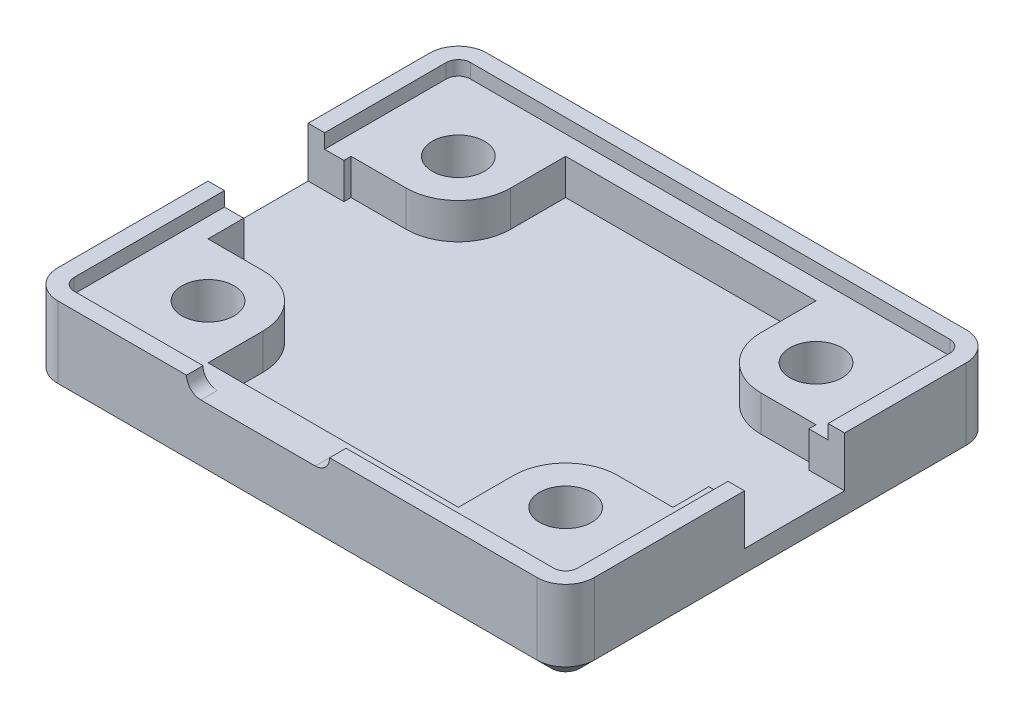
SolidWorks part; units mm, degrees
ref_plane "Front Plane" through (0, 0, 0) normal (0, 0, 1) x (1, 0, 0)
ref_plane "Top Plane" through (0, 0, 0) normal (0, 1, 0) x (1, 0, 0)
ref_plane "Right Plane" through (0, 0, 0) normal (1, 0, 0) x (0, 0, -1)
sketch "Sketch1" plane through (0, 0, 0) normal (0, 1, 0) x (1, 0, 0)
  line L1 (-16.75, -15) -> (16.75, -15)
  line L2 (-18.75, -13) -> (-18.75, 13)
  line L3 (-16.75, 15) -> (16.75, 15)
  line L4 (18.75, -13) -> (18.75, 13)
  line L5 (-18.75, -15) -> (18.75, 15) construction
  line L6 (-18.75, 15) -> (18.75, -15) construction
  arc A0 (16.75, 15) -> (18.75, 13) centre (16.75, 13) cw
  arc A1 (16.75, -15) -> (18.75, -13) centre (16.75, -13) ccw
  arc A2 (-16.75, -15) -> (-18.75, -13) centre (-16.75, -13) cw
  arc A3 (-18.75, 13) -> (-16.75, 15) centre (-16.75, 13) cw
  point P0 (0, 0)
  dimension "D3" = 2
  dimension "D1" = 37.5
  dimension "D2" = 30
extrude "Boss-Extrude1" add sketch "Sketch1" along normal blind 6
sketch "Sketch2" plane through (0, 6, 0) normal (0, 1, 0) x (1, 0, 0)
  line L0 (0, -15.0633) -> (0, 14.9367) construction
  line L1 (-16.25, -12.5) -> (16.25, -12.5) construction
  line L2 (-16.25, -12.5) -> (-16.25, 12.5) construction
  line L3 (-16.25, 12.5) -> (16.25, 12.5) construction
  line L4 (16.25, -12.5) -> (16.25, 12.5) construction
  line L5 (-16.25, -12.5) -> (16.25, 12.5) construction
  line L6 (-16.25, 12.5) -> (16.25, -12.5) construction
  line L7 (-16.25, 12.5) -> (-8.75, 12.5)
  line L8 (-16.25, 12.5) -> (-16.25, 5)
  line L9 (-16.25, 5) -> (-8.75, 5)
  line L10 (-8.75, 12.5) -> (-8.75, 5)
  line L11 (18.75, 0) -> (-18.75, 0) construction
  line L12 (16.25, 12.5) -> (8.75, 12.5)
  line L13 (8.75, 12.5) -> (8.75, 5)
  line L14 (16.25, 5) -> (8.75, 5)
  line L15 (16.25, 12.5) -> (16.25, 5)
  line L16 (16.25, -12.5) -> (8.75, -12.5)
  line L17 (16.25, -12.5) -> (16.25, -5)
  line L18 (16.25, -5) -> (8.75, -5)
  line L19 (8.75, -12.5) -> (8.75, -5)
  line L20 (-16.25, -12.5) -> (-8.75, -12.5)
  line L21 (-16.25, -12.5) -> (-16.25, -5)
  line L22 (-16.25, -5) -> (-8.75, -5)
  line L23 (-8.75, -12.5) -> (-8.75, -5)
  line L24 (-8.75, 12.5) -> (8.75, 12.5)
  line L25 (16.25, -5) -> (16.25, 5)
  line L26 (-16.25, -5) -> (-16.25, 5)
  line L27 (-8.75, -12.5) -> (8.75, -12.5)
  circle A0 centre (-12.5, 8.75) radius 1.825
  circle A1 centre (12.5, 8.75) radius 1.825
  circle A2 centre (12.5, -8.75) radius 1.825
  circle A3 centre (-12.5, -8.75) radius 1.825
  point P0 (0, 0)
  point P23 (-12.5, 5)
  dimension "D5" = 3.65
  dimension "D1" = 32.5
  dimension "D2" = 25
  dimension "D3" = 7.5
  dimension "D4" = 7.5
  dimension "D6" = 3.75
  dimension "D7" = 3.75
extrude "Cut-Extrude3" cut sketch "Sketch2" against normal blind 3.5 contours A0 | A3 | L23 L27 L19 L18 L25 L14 L13 L24 L10 L9 L26 L22 | A2 | A1 region at (0, 6, 0) region at (-12.5, 6, -8.75) region at (12.5, 6, -8.75) region at (12.5, 6, 8.75) region at (-12.5, 6, 8.75)
sketch "Sketch3" plane through (0, 6, 0) normal (0, 1, 0) x (1, 0, 0)
  circle A0 centre (-12.5, 8.75) radius 1.825
  circle A1 centre (-12.5, -8.75) radius 1.825
  circle A2 centre (12.5, -8.75) radius 1.825
  circle A3 centre (12.5, 8.75) radius 1.825
extrude "Cut-Extrude4" cut sketch "Sketch3" against normal blind 13.5
sketch "Sketch4" plane through (0, 6, 0) normal (0, 1, 0) x (1, 0, 0)
  line L1 (-16.25, -12.5) -> (16.25, -12.5)
  line L2 (-16.25, -12.5) -> (-16.25, 12.5)
  line L3 (-16.25, 12.5) -> (16.25, 12.5)
  line L4 (16.25, -12.5) -> (16.25, 12.5)
  line L5 (-16.25, -12.5) -> (16.25, 12.5) construction
  line L6 (-16.25, 12.5) -> (16.25, -12.5) construction
  point P0 (0, 0)
  dimension "D1" = 25
  dimension "D2" = 32.5
extrude "Cut-Extrude5" cut sketch "Sketch4" against normal blind 1
sketch "Sketch5" plane through (0, 6, 0) normal (0, 1, 0) x (1, 0, 0)
  line L0 (-16.25, 4.5) -> (-16.25, -2.5)
  line L1 (-16.25, 12.5) -> (-16.25, 5) construction
  line L2 (-16.25, -5) -> (-16.25, 5) construction
  line L3 (-16.25, 4.5) -> (-18.75, 4.5)
  line L4 (-18.75, 13) -> (-18.75, -13) construction
  line L5 (-18.75, 4.5) -> (-18.75, -2.5)
  line L6 (-18.75, -2.5) -> (-16.25, -2.5)
  line L7 (0, -3.3) -> (0, 3.3) construction
  line L8 (16.25, 4.5) -> (16.25, -2.5)
  line L9 (18.75, 4.5) -> (18.75, -2.5)
  line L10 (16.25, 4.5) -> (18.75, 4.5)
  line L11 (18.75, -2.5) -> (16.25, -2.5)
  dimension "D1" = 7
  dimension "D2" = 8
extrude "Cut-Extrude6" cut sketch "Sketch5" against normal blind 3.5
sketch "Sketch6" plane through (0, 6, 0) normal (0, 1, 0) x (1, 0, 0)
  line L0 (18.75, 4.5) -> (18.75, 13) construction
  line L1 (16.75, 15) -> (-16.75, 15) construction
  line L2 (-18.75, 13) -> (-18.75, 4.5) construction
  line L3 (18.75, 4.5) -> (18.75, 13)
  line L4 (16.75, 15) -> (-16.75, 15)
  line L5 (-18.75, 13) -> (-18.75, 4.5)
  line L6 (17.6, 4.5) -> (17.6, 13)
  line L7 (16.75, 13.85) -> (-16.75, 13.85)
  line L8 (-17.6, 13) -> (-17.6, 4.5)
  line L9 (-3.3, 0) -> (3.3, 0) construction
  line L10 (-17.6, -13) -> (-17.6, -4.5)
  line L11 (16.75, -13.85) -> (-16.75, -13.85)
  line L12 (17.6, -4.5) -> (17.6, -13)
  line L13 (-18.75, -13) -> (-18.75, -4.5)
  line L14 (16.75, -15) -> (-16.75, -15)
  line L15 (18.75, -4.5) -> (18.75, -13)
  line L16 (-18.75, -4.5) -> (-18.75, -2.5)
  line L17 (-18.75, -2.5) -> (-17.6, -2.5)
  line L18 (-18.75, -2.5) -> (-16.25, -2.5) construction
  line L19 (-17.6, -2.5) -> (-17.6, -4.5)
  line L20 (17.6, -4.5) -> (17.6, -2.5)
  line L21 (16.25, -2.5) -> (18.75, -2.5) construction
  line L22 (17.6, -2.5) -> (18.75, -2.5)
  line L23 (18.75, -2.5) -> (18.75, -4.5)
  line L24 (-16.25, 4.5) -> (-16.25, 12.5)
  line L25 (-16.25, 12.5) -> (16.25, 12.5)
  line L26 (16.25, 12.5) -> (16.25, 4.5)
  line L27 (16.25, 4.5) -> (17.6, 4.5)
  line L28 (16.25, -2.5) -> (17.6, -2.5)
  line L29 (16.25, -2.5) -> (16.25, -12.5)
  line L30 (16.25, -12.5) -> (-16.25, -12.5)
  line L31 (-16.25, -12.5) -> (-16.25, -2.5)
  line L32 (-16.25, -2.5) -> (-17.6, -2.5)
  arc A0 (18.75, 13) -> (16.75, 15) centre (16.75, 13) ccw construction
  arc A1 (-16.75, 15) -> (-18.75, 13) centre (-16.75, 13) ccw construction
  arc A2 (18.75, 13) -> (16.75, 15) centre (16.75, 13) ccw
  arc A3 (-16.75, 15) -> (-18.75, 13) centre (-16.75, 13) ccw
  arc A4 (17.6, 13) -> (16.75, 13.85) centre (16.75, 13) ccw
  arc A5 (-16.75, 13.85) -> (-17.6, 13) centre (-16.75, 13) ccw
  arc A6 (-16.75, -13.85) -> (-17.6, -13) centre (-16.75, -13) cw
  arc A7 (17.6, -13) -> (16.75, -13.85) centre (16.75, -13) cw
  arc A8 (-16.75, -15) -> (-18.75, -13) centre (-16.75, -13) cw
  arc A9 (18.75, -13) -> (16.75, -15) centre (16.75, -13) cw
  line M3 (-18.75, 4.5) -> (-16.25, 4.5)
  line M4 (-16.25, 4.5) -> (-16.25, 12.5)
  line M5 (-16.25, 12.5) -> (16.25, 12.5)
  line M6 (16.25, 12.5) -> (16.25, 4.5)
  line M7 (16.25, 4.5) -> (18.75, 4.5)
  dimension "D1" = 1.15
extrude "Cut-Extrude7" cut sketch "Sketch6" against normal blind 1 contours L7 A5 L8 L6 A4 M3 M4 M5 M6 M7 | A7 L12 L20 L28 L29 L30 L31 L32 L19 L10 A6 L11 region at (16.925, 6, -4.8642) region at (-17.2302, 6, 8.75)
fillet "Fillet1" radius 3.65 4 edges at (8.75, 3.75, 5) (-8.75, 3.75, 5) (8.75, 3.75, -5) (-8.75, 3.75, -5)
chamfer "Chamfer1" distance 1 angle 45 8 edges at (18.75, 0, 0) (18.1642, 0, -14.4142) (18.1642, 0, 14.4142) (0, 0, -15) (0, 0, 15) (-18.1642, 0, -14.4142) (-18.1642, 0, 14.4142) (-18.75, 0, 0)
sketch "Sketch7" plane through (0, 0, 15) normal (0, 0, 1) x (1, 0, 0)
  line L0 (-18.75, 6) -> (-7.75, 6) construction
  line L1 (-16.75, 6) -> (16.75, 6) construction
  line L2 (-6.75, 6) -> (1.25, 6) construction
  line L3 (-6.75, 7) -> (1.25, 7)
  line L4 (-6.75, 5) -> (1.25, 5)
  arc A0 (-6.75, 7) -> (-6.75, 5) centre (-6.75, 6) ccw
  arc A1 (1.25, 5) -> (1.25, 7) centre (1.25, 6) ccw
  point P7 (-2.75, 6)
  dimension "D1" = 11
  dimension "D2" = 2
  dimension "D3" = 8
  dimension "D4" = 1
extrude "Cut-Extrude8" cut sketch "Sketch7" against normal blind 10
